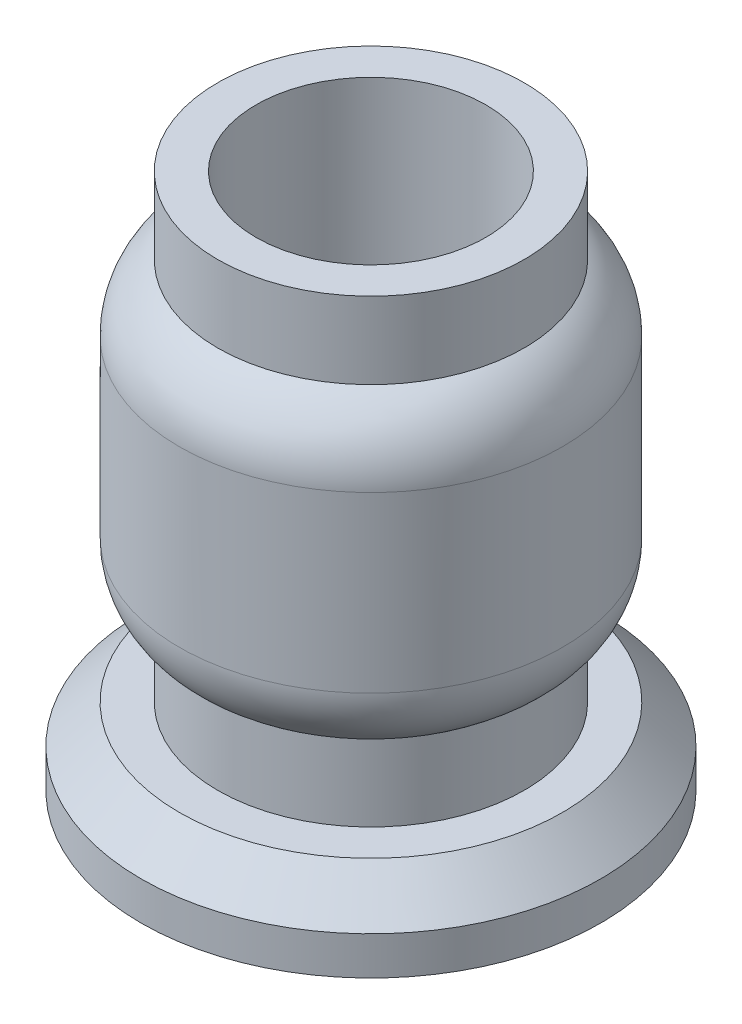
SolidWorks part; units mm, degrees
material "AISI 316 Annealed Stainless Steel Bar (SS)"
ref_plane "Front Plane" through (0, 0, 0) normal (0, 0, 1) x (1, 0, 0)
ref_plane "Top Plane" through (0, 0, 0) normal (0, 1, 0) x (1, 0, 0)
ref_plane "Right Plane" through (0, 0, 0) normal (1, 0, 0) x (0, 0, -1)
sketch "Sketch1" plane through (0, 0, 0) normal (0, 1, 0) x (1, 0, 0)
  circle A0 centre (0, 0) radius 3
  dimension "D1" = 6
extrude "Boss-Extrude1" add sketch "Sketch1" along normal blind 1
chamfer "Chamfer1" distance 0.5 angle 45 1 edges at (0, 1, 3)
sketch "Sketch2" plane through (0, 1, 0) normal (0, 1, 0) x (1, 0, 0)
  circle A0 centre (0, 0) radius 2
  dimension "D1" = 4
extrude "Boss-Extrude2" add sketch "Sketch2" along normal blind 1
sketch "Sketch3" plane through (0, 2, 0) normal (0, 1, 0) x (1, 0, 0)
  circle A0 centre (0, 0) radius 2.5
  dimension "D1" = 5
extrude "Boss-Extrude3" add sketch "Sketch3" along normal blind 4
sketch "Sketch4" plane through (0, 6, 0) normal (0, 1, 0) x (1, 0, 0)
  circle A0 centre (0, 0) radius 2
  dimension "D1" = 4
extrude "Boss-Extrude4" add sketch "Sketch4" along normal blind 1
fillet "Fillet1" radius 1 1 edges at (0, 6, 2.5)
fillet "Fillet2" radius 1 1 edges at (0, 2, 2.5)
sketch "Sketch5" plane through (0, 0, 0) normal (0, -1, 0) x (1, 0, 0)
  circle A0 centre (0, 0) radius 1.5
  dimension "D1" = 3
extrude "Cut-Extrude1" cut sketch "Sketch5" against normal blind 10
